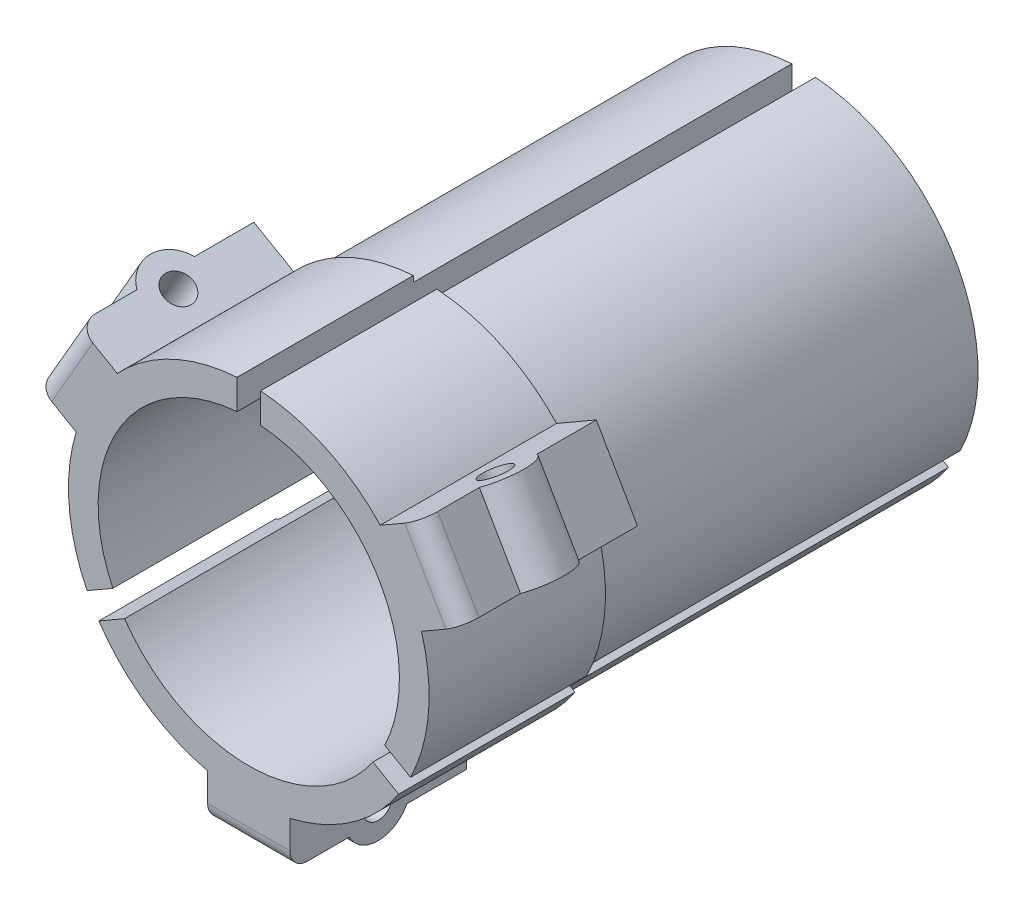
SolidWorks part; units mm, degrees
ref_plane "Front Plane" through (0, 0, 0) normal (0, 0, 1) x (1, 0, 0)
ref_plane "Top Plane" through (0, 0, 0) normal (0, 1, 0) x (1, 0, 0)
ref_plane "Right Plane" through (0, 0, 0) normal (1, 0, 0) x (0, 0, -1)
sketch "Sketch1" plane through (0, 0, 0) normal (0, 0, 1) x (1, 0, 0)
  line L1 (-0.254, 3.7607) -> (-0.254, 3.245)
  line L2 (0.254, 3.7607) -> (0.254, 3.245)
  line L3 (3.1299, -2.1003) -> (2.6832, -1.8425)
  line L4 (3.3839, -1.6604) -> (2.9372, -1.4025)
  line L5 (-3.3839, -1.6604) -> (-2.9372, -1.4025)
  line L6 (-3.1299, -2.1003) -> (-2.6832, -1.8425)
  arc A0 (-0.254, 3.7607) -> (-3.3839, -1.6604) centre (0, 0) ccw
  arc A1 (-0.254, 3.245) -> (-2.9372, -1.4025) centre (0, 0) ccw
  arc A2 (-2.6832, -1.8425) -> (2.6832, -1.8425) centre (0, 0) ccw
  circle A3 centre (0, 0) radius 3.7693 construction
  circle A4 centre (0, 0) radius 3.2549 construction
  arc A5 (-3.1299, -2.1003) -> (3.1299, -2.1003) centre (0, 0) ccw
  arc A6 (2.9372, -1.4025) -> (0.254, 3.245) centre (0, 0) ccw
  arc A7 (3.3839, -1.6604) -> (0.254, 3.7607) centre (0, 0) ccw
  point P1 (3.1127, 0.9516)
  point P6 (3.6046, 1.102)
  point P21 (0, 0)
  dimension "D1" = 3
extrude "Boss-Extrude1" add sketch "Sketch1" along normal blind 11.9888
sketch "Sketch2" plane through (0, 0, 11.9888) normal (0, 0, 1) x (1, 0, 0)
  line L0 (-0.254, 3.245) -> (-0.254, 3.7607) construction
  line L1 (-3.3839, -1.6604) -> (-2.9372, -1.4025) construction
  line L2 (-0.254, 3.7607) -> (-0.254, 3.888)
  line L3 (-3.4941, -1.724) -> (-3.3839, -1.6604)
  line L4 (0.254, 3.888) -> (0.254, 3.7607)
  line L5 (3.3839, -1.6604) -> (3.4941, -1.724)
  line L6 (-0.254, 3.245) -> (-0.254, 3.7607) construction
  line L7 (-3.3839, -1.6604) -> (-2.9372, -1.4025) construction
  line L8 (-0.127, 3.245) -> (-0.127, 3.8942) construction
  line L9 (-3.436, -1.8371) -> (-2.8737, -1.5125) construction
  line L10 (3.2401, -2.164) -> (3.1299, -2.1003)
  line L11 (-3.1299, -2.1003) -> (-3.2401, -2.164)
  arc A0 (-0.254, 3.7607) -> (-3.3839, -1.6604) centre (0, 0) ccw construction
  arc A1 (-0.254, 3.7607) -> (-3.3839, -1.6604) centre (0, 0) ccw
  arc A2 (-0.254, 3.888) -> (-3.4941, -1.724) centre (0, 0) ccw
  arc A3 (3.4941, -1.724) -> (0.254, 3.888) centre (0, 0) ccw
  arc A4 (-0.127, 3.8942) -> (-3.436, -1.8371) centre (0, 0) ccw construction
  arc A5 (-3.2401, -2.164) -> (3.2401, -2.164) centre (0, 0) ccw
  arc A6 (3.3839, -1.6604) -> (0.254, 3.7607) centre (0, 0) ccw construction
  arc A7 (-3.1299, -2.1003) -> (3.1299, -2.1003) centre (0, 0) ccw construction
  arc A8 (3.3839, -1.6604) -> (0.254, 3.7607) centre (0, 0) ccw
  arc A9 (-3.1299, -2.1003) -> (3.1299, -2.1003) centre (0, 0) ccw
  point P23 (0, 0)
  dimension "D1" = 3
extrude "Boss-Extrude2" add sketch "Sketch2" against normal blind 3.81
sketch "Sketch4" plane through (0, 0, 11.9888) normal (0, 0, 1) x (1, 0, 0)
  line L0 (-2.8408, 2.6666) -> (-3.6997, 3.1625)
  line L1 (-0.889, -3.7935) -> (-0.889, -4.7853)
  line L2 (0.889, -3.7935) -> (0.889, -4.7853)
  line L3 (-0.889, -4.7853) -> (0.889, -4.7853)
  line L4 (-3.6997, 3.1625) -> (-4.5887, 1.6227)
  line L5 (-3.7298, 1.1269) -> (-4.5887, 1.6227)
  line L6 (3.7298, 1.1269) -> (4.5887, 1.6227)
  line L7 (4.5887, 1.6227) -> (3.6997, 3.1625)
  line L8 (2.8408, 2.6666) -> (3.6997, 3.1625)
  arc A0 (-3.2401, -2.164) -> (3.2401, -2.164) centre (0, 0) ccw construction
  arc A1 (-0.889, -3.7935) -> (0.889, -3.7935) centre (0, 0) ccw
  arc A2 (-2.8408, 2.6666) -> (-3.7298, 1.1269) centre (0, 0) ccw
  arc A3 (3.7298, 1.1269) -> (2.8408, 2.6666) centre (0, 0) ccw
  point P0 (0, -3.8963)
  point P20 (0, 0)
  point P25 (0, 0)
  dimension "D2" = 3
  dimension "D1" = 0.889
  dimension "D3" = 3
extrude "Boss-Extrude3" add sketch "Sketch4" against normal blind 3.81
fillet "Fillet1" radius 0.381 1 edges at (-4.1442, 2.3926, 11.9888)
fillet "Fillet2" radius 0.381 1 edges at (0, -4.7853, 11.9888)
fillet "Fillet3" radius 0.381 1 edges at (4.1442, 2.3926, 11.9888)
sketch "Sketch5" plane through (-0.4445, 0.7699, 0) normal (-0.5, 0.866, 0) x (0.866, 0.5, 0)
  line L0 (4.4043, -11.9888) -> (3.7935, -11.9888) construction
  line L4 (4.7853, -8.1788) -> (4.7853, -11.6078) construction
  line L5 (4.7853, -9.4616) -> (4.7853, -10.706)
  circle A0 centre (4.4678, -10.0838) radius 0.3175
  arc A1 (4.7853, -10.706) -> (4.7853, -9.4616) centre (4.4678, -10.0838) ccw
  circle A3 centre (4.4678, -10.0838) radius 0.6985 construction
  point P13 (5.1663, -10.0838)
  line M5 (4.7853, -11.6078) -> (4.7853, -8.1788)
  dimension "D1" = 0.635
  dimension "D2" = 1.905
  dimension "D3" = 0.381
extrude "Boss-Extrude4" add sketch "Sketch5" against normal blind 1.778 contours A1 L5 M5 region at (3.8353, 3.2409, 10.0838)
extrude "Cut-Extrude1" cut sketch "Sketch5<6>" against normal blind 1.778 contours A0
sketch "Sketch5<6>" plane through (-0.4445, 0.7699, 0) normal (-0.5, 0.866, 0) x (0.866, 0.5, 0) same geometry as "Sketch5"
sketch "Sketch6" plane through (-0.4445, -0.7699, 0) normal (-0.5, -0.866, 0) x (0.866, -0.5, 0)
  line L1 (-4.7853, 8.1788) -> (-4.7853, 11.6078) construction
  line L2 (-4.7853, 9.4616) -> (-4.7853, 10.706)
  circle A0 centre (-4.4678, 10.0838) radius 0.3175
  arc A1 (-4.7853, 10.706) -> (-4.7853, 9.4616) centre (-4.4678, 10.0838) ccw
  circle A3 centre (-4.4678, 10.0838) radius 0.6985 construction
  point P6 (-3.7693, 10.0838)
  line M3 (-4.7853, 11.6078) -> (-4.7853, 8.1788)
  dimension "D1" = 0.381
extrude "Boss-Extrude5" add sketch "Sketch6" against normal blind 1.778 contours A1 L2 M3 region at (-4.7243, 1.7011, 10.0838)
extrude "Cut-Extrude2" cut sketch "Sketch6<3>" against normal through all contours A0 region at (-4.3137, 1.464, 10.0838)
sketch "Sketch6<3>" plane through (-0.4445, -0.7699, 0) normal (-0.5, -0.866, 0) x (0.866, -0.5, 0) same geometry as "Sketch6"
sketch "Sketch7" plane through (0.889, 0, 0) normal (1, 0, 0) x (0, 0, -1)
  line L1 (-8.1788, -4.7853) -> (-11.6078, -4.7853) construction
  line L2 (-9.4616, -4.7853) -> (-10.706, -4.7853)
  circle A0 centre (-10.0838, -4.4678) radius 0.3175
  arc A1 (-10.706, -4.7853) -> (-9.4616, -4.7853) centre (-10.0838, -4.4678) ccw
  circle A3 centre (-10.0838, -4.4678) radius 0.6985 construction
  point P6 (-9.3853, -4.4678)
  line M3 (-11.6078, -4.7853) -> (-8.1788, -4.7853)
  dimension "D1" = 0.381
extrude "Boss-Extrude6" add sketch "Sketch7" against normal blind 1.778 contours A1 L2 M3 region at (0.889, -4.9419, 10.0838)
extrude "Cut-Extrude3" cut sketch "Sketch7<3>" against normal through all contours A0 region at (0.889, -4.4678, 10.0838)
sketch "Sketch7<3>" plane through (0.889, 0, 0) normal (1, 0, 0) x (0, 0, -1) same geometry as "Sketch7"
